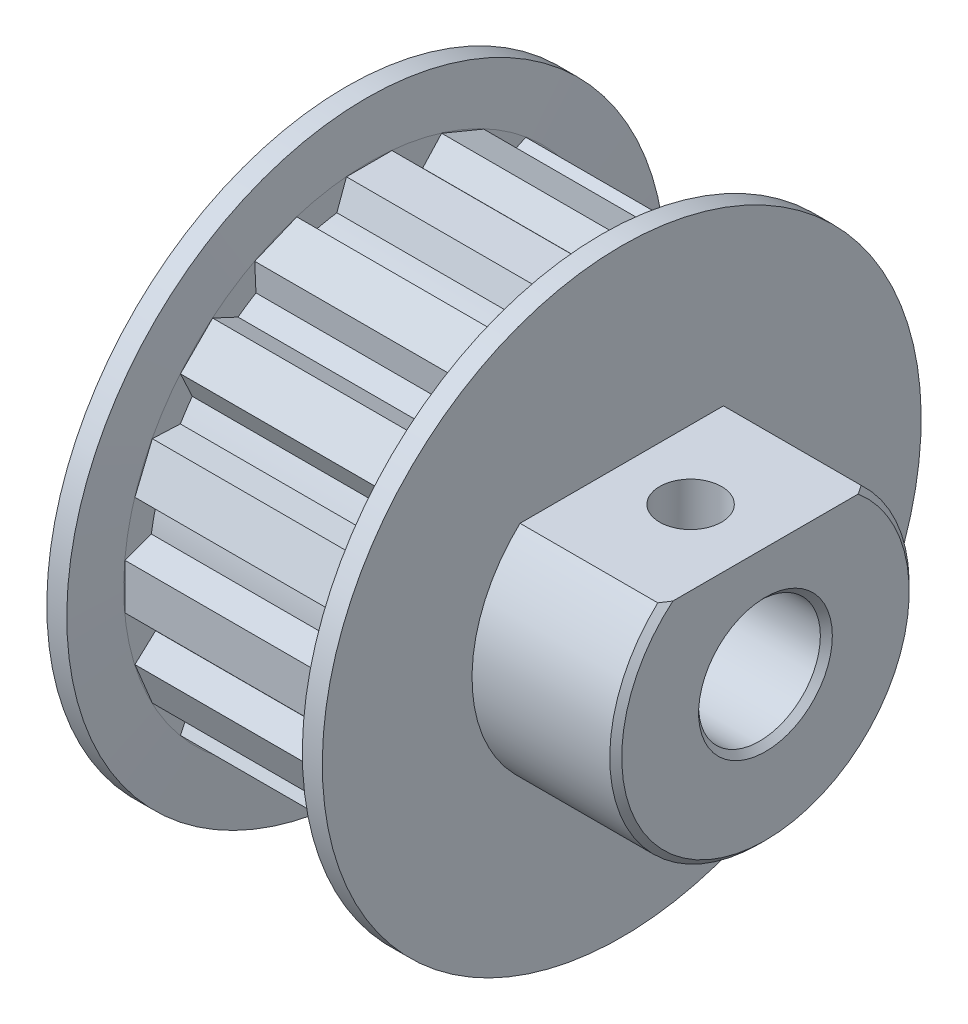
SolidWorks part; units mm, degrees
ref_plane "Front Plane" through (0, 0, 0) normal (0, 0, 1) x (1, 0, 0)
ref_plane "Top Plane" through (0, 0, 0) normal (0, 1, 0) x (1, 0, 0)
ref_plane "Right Plane" through (0, 0, 0) normal (1, 0, 0) x (0, 0, -1)
sketch "Sketch1" plane through (0, 0, 0) normal (0, 0, 1) x (1, 0, 0)
  line L0 (0, 15) -> (0, 0)
  line L1 (0, 0) -> (13.8, 0)
  line L2 (13.8, 0) -> (13.8, 15)
  line L3 (13.8, 15) -> (12.8, 15)
  line L4 (12.8, 15) -> (12.65, 12.3)
  line L5 (12.65, 12.3) -> (12.65, 11.0324)
  line L6 (12.65, 11.0324) -> (1.15, 11.0324)
  line L7 (1.15, 11.0324) -> (1.15, 12.3)
  line L8 (1.15, 12.3) -> (1, 15)
  line L9 (1, 15) -> (0, 15)
  line L10 (0, 0) -> (13.8, 0) construction
  dimension "D1" = 11.5
  dimension "D2" = 13.8
  dimension "D3" = 1.15
revolve "Revolve1" add sketch "Sketch1" angle 360 about L10 reverse direction yes
sketch "Sketch2" plane through (13.8, 0, 0) normal (1, 0, 0) x (0, 0, -1)
  circle A0 centre (0, 0) radius 7.5
extrude "Boss-Extrude1" add sketch "Sketch2" along normal blind 7.2
hole_wizard "Ø6.0 (6) Diameter Hole1" positions "Sketch4" profile "Sketch3" hole size "Ø6.0" standard "ANSI Metric"
sketch "Sketch4" plane through (21, 0, 0) normal (1, 0, 0) x (0, 0, -1)
  point P0 (0, 0)
sketch "Sketch3" plane through (21, 0, 0) normal (0, 1, 0) x (0, 0, -1)
  line L0 (0, 0) -> (0, 21)
  line L1 (0, 21) -> (3.05, 21)
  line L2 (3.05, 21) -> (3.05, 0)
  line L5 (3.05, 0) -> (0, 0)
  line L11 (0, -6.35) -> (0, 107.95) construction
  dimension "Thru Hole Dia." = 6.1
  dimension "Thru Hole Depth" = 21
ref_plane "Plane1" through (0, 0, 0) normal (0, -1, 0) x (1, 0, 0)
sketch "Sketch5" plane through (0, 0, 0) normal (0, -1, 0) x (1, 0, 0)
  line L0 (12.65, 12.2324) -> (1.15, 12.2324)
rib "Rib1" sketch "Sketch5" sketch "Sketch5" thickness 2.2803 extrusion direction parallel to sketch draft on yes draft angle 20 parameters "D1"=2.2803, "D3"=20
ref_plane "Plane2" through (0, 0, 0) normal (0, 0, -1) x (-1, 0, 0)
sketch "Sketch6" plane through (0, 0, 0) normal (0, 0, -1) x (-1, 0, 0)
  line L0 (-12.65, -12.2324) -> (-1.15, -12.2324)
rib "Rib2" sketch "Sketch6" sketch "Sketch6" thickness 2.2803 extrusion direction parallel to sketch draft on yes draft angle 20 parameters "D1"=2.2803, "D3"=20
sketch "Sketch7" plane through (0, 0, 0) normal (0, 1, 0) x (1, 0, 0)
  line L0 (12.65, 12.2324) -> (1.15, 12.2324)
rib "Rib3" sketch "Sketch7" sketch "Sketch7" thickness 2.2803 extrusion direction parallel to sketch draft on yes draft angle 20 parameters "D1"=2.2803, "D3"=20
sketch "Sketch8" plane through (0, 0, 0) normal (0, 0, 1) x (1, 0, 0)
  line L0 (12.65, 12.2324) -> (1.15, 12.2324)
rib "Rib4" sketch "Sketch8" sketch "Sketch8" thickness 2.2803 extrusion direction parallel to sketch draft on yes draft angle 20 parameters "D1"=2.2803, "D3"=20
ref_plane "Plane3" through (0, 0, 0) normal (0, -0.9239, -0.3827) x (1, 0, 0)
sketch "Sketch9" plane through (0, 0, 0) normal (0, -0.9239, -0.3827) x (1, 0, 0)
  line L0 (12.65, 12.2324) -> (1.15, 12.2324)
rib "Rib5" sketch "Sketch9" sketch "Sketch9" thickness 2.2803 extrusion direction parallel to sketch draft on yes draft angle 20 parameters "D1"=2.2803, "D3"=20
ref_plane "Plane4" through (0, 0, 0) normal (0, 0.9239, -0.3827) x (-1, 0, 0)
sketch "Sketch10" plane through (0, 0, 0) normal (0, 0.9239, -0.3827) x (-1, 0, 0)
  line L0 (-12.65, -12.2324) -> (-1.15, -12.2324)
rib "Rib6" sketch "Sketch10" sketch "Sketch10" thickness 2.2803 extrusion direction parallel to sketch draft on yes draft angle 20 parameters "D1"=2.2803, "D3"=20
ref_plane "Plane5" through (0, 0, 0) normal (0, -0.3827, -0.9239) x (1, 0, 0)
sketch "Sketch11" plane through (0, 0, 0) normal (0, -0.3827, -0.9239) x (1, 0, 0)
  line L0 (12.65, 12.2324) -> (1.15, 12.2324)
rib "Rib7" sketch "Sketch11" sketch "Sketch11" thickness 2.2803 extrusion direction parallel to sketch draft on yes draft angle 20 parameters "D1"=2.2803, "D3"=20
ref_plane "Plane6" through (0, 0, 0) normal (0, 0.7071, -0.7071) x (-1, 0, 0)
sketch "Sketch12" plane through (0, 0, 0) normal (0, 0.7071, -0.7071) x (-1, 0, 0)
  line L0 (-12.65, -12.2324) -> (-1.15, -12.2324)
rib "Rib8" sketch "Sketch12" sketch "Sketch12" thickness 2.2803 extrusion direction parallel to sketch draft on yes draft angle 20 parameters "D1"=2.2803, "D3"=20
ref_plane "Plane7" through (0, 0, 0) normal (0, -0.7071, 0.7071) x (1, 0, 0)
sketch "Sketch13" plane through (0, 0, 0) normal (0, -0.7071, 0.7071) x (1, 0, 0)
  line L0 (12.65, 12.2324) -> (1.15, 12.2324)
rib "Rib9" sketch "Sketch13" sketch "Sketch13" thickness 2.2803 extrusion direction parallel to sketch draft on yes draft angle 20 parameters "D1"=2.2803, "D3"=20
ref_plane "Plane8" through (0, 0, 0) normal (0, 0.3827, -0.9239) x (-1, 0, 0)
sketch "Sketch14" plane through (0, 0, 0) normal (0, 0.3827, -0.9239) x (-1, 0, 0)
  line L0 (-12.65, -12.2324) -> (-1.15, -12.2324)
rib "Rib10" sketch "Sketch14" sketch "Sketch14" thickness 2.2803 extrusion direction parallel to sketch draft on yes draft angle 20 parameters "D1"=2.2803, "D3"=20
ref_plane "Plane9" through (0, 0, 0) normal (0, -0.7071, -0.7071) x (1, 0, 0)
sketch "Sketch15" plane through (0, 0, 0) normal (0, -0.7071, -0.7071) x (1, 0, 0)
  line L0 (12.65, 12.2324) -> (1.15, 12.2324)
rib "Rib11" sketch "Sketch15" sketch "Sketch15" thickness 2.2803 extrusion direction parallel to sketch draft on yes draft angle 20 parameters "D1"=2.2803, "D3"=20
ref_plane "Plane10" through (0, 0, 0) normal (0, 0.7071, 0.7071) x (-1, 0, 0)
sketch "Sketch16" plane through (0, 0, 0) normal (0, 0.7071, 0.7071) x (-1, 0, 0)
  line L0 (-12.65, -12.2324) -> (-1.15, -12.2324)
rib "Rib12" sketch "Sketch16" sketch "Sketch16" thickness 2.2803 extrusion direction parallel to sketch draft on yes draft angle 20 parameters "D1"=2.2803, "D3"=20
ref_plane "Plane11" through (0, 0, 0) normal (0, 0.9239, 0.3827) x (-1, 0, 0)
sketch "Sketch17" plane through (0, 0, 0) normal (0, 0.9239, 0.3827) x (-1, 0, 0)
  line L0 (-12.65, -12.2324) -> (-1.15, -12.2324)
rib "Rib13" sketch "Sketch17" sketch "Sketch17" thickness 2.2803 extrusion direction parallel to sketch draft on yes draft angle 20 parameters "D1"=2.2803, "D3"=20
ref_plane "Plane12" through (0, 0, 0) normal (0, -0.3827, 0.9239) x (1, 0, 0)
sketch "Sketch18" plane through (0, 0, 0) normal (0, -0.3827, 0.9239) x (1, 0, 0)
  line L0 (12.65, 12.2324) -> (1.15, 12.2324)
rib "Rib14" sketch "Sketch18" sketch "Sketch18" thickness 2.2803 extrusion direction parallel to sketch draft on yes draft angle 20 parameters "D1"=2.2803, "D3"=20
ref_plane "Plane13" through (0, 0, 0) normal (0, 0.3827, 0.9239) x (-1, 0, 0)
sketch "Sketch19" plane through (0, 0, 0) normal (0, 0.3827, 0.9239) x (-1, 0, 0)
  line L0 (-12.65, -12.2324) -> (-1.15, -12.2324)
rib "Rib15" sketch "Sketch19" sketch "Sketch19" thickness 2.2803 extrusion direction parallel to sketch draft on yes draft angle 20 parameters "D1"=2.2803, "D3"=20
ref_plane "Plane14" through (0, 0, 0) normal (0, -0.9239, 0.3827) x (1, 0, 0)
sketch "Sketch20" plane through (0, 0, 0) normal (0, -0.9239, 0.3827) x (1, 0, 0)
  line L0 (12.65, 12.2324) -> (1.15, 12.2324)
rib "Rib16" sketch "Sketch20" sketch "Sketch20" thickness 2.2803 extrusion direction parallel to sketch draft on yes draft angle 20 parameters "D1"=2.2803, "D3"=20
chamfer "Chamfer1" distance 0.3 angle 45 3 edges at (21, 0, -7.5) (0, 0, -3.05) (21, 0, -3.05)
sketch "Sketch21" plane through (21, 0, 0) normal (1, 0, 0) x (0, 0, -1)
  line L0 (-5.095, 5.5037) -> (5.095, 5.5037)
  line L1 (-5.095, 5.5037) -> (-5.095, 7.871)
  line L2 (5.095, 5.5037) -> (5.095, 7.871)
  line L3 (-5.095, 7.871) -> (5.095, 7.871)
  circle A0 centre (0, 0) radius 7.5 construction
extrude "Cut-Extrude1" cut sketch "Sketch21" against normal blind 7.2
sketch "Sketch22" plane through (0, 5.5037, 0) normal (0, 1, 0) x (1, 0, 0)
  line L0 (21, 0) -> (13.8, 0) construction
  line L1 (21, -4.6421) -> (21, 4.6421) construction
  line L2 (13.8, -15) -> (13.8, 15) construction
  line L3 (17.25, 5.095) -> (17.25, -5.095) construction
  line L4 (13.8, 5.095) -> (20.7, 5.095) construction
  line L5 (13.8, -5.095) -> (20.7, -5.095) construction
  circle A0 centre (17.25, 0) radius 1.55
  dimension "D1" = 3.1
extrude "Cut-Extrude2" cut sketch "Sketch22" against normal blind 5.2
